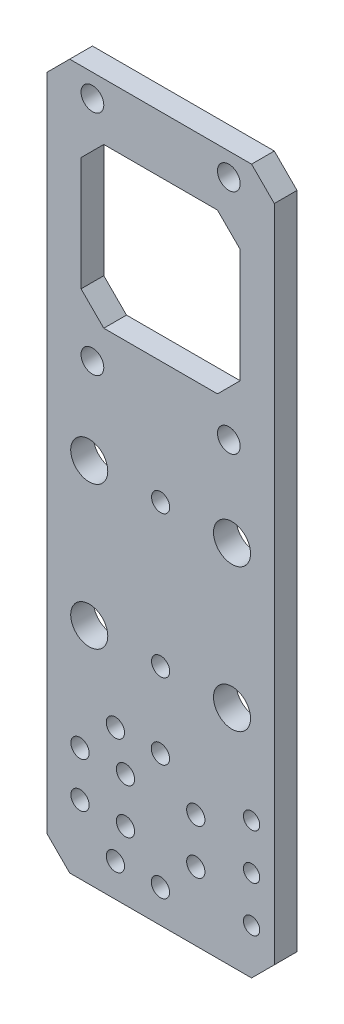
SolidWorks part; units mm, degrees
material "5052-O"
ref_plane "Front Plane" through (0, 0, 0) normal (0, 0, 1) x (1, 0, 0)
ref_plane "Top Plane" through (0, 0, 0) normal (0, 1, 0) x (1, 0, 0)
ref_plane "Right Plane" through (0, 0, 0) normal (1, 0, 0) x (0, 0, -1)
sketch "Sketch1" plane through (0, 0, 0) normal (0, 0, 1) x (1, 0, 0)
  line L1 (-31.75, -82.55) -> (31.75, -82.55)
  line L2 (-31.75, -82.55) -> (-31.75, 114.3)
  line L3 (-31.75, 114.3) -> (31.75, 114.3)
  line L4 (31.75, -82.55) -> (31.75, 114.3)
  line L5 (-31.75, -82.55) -> (31.75, 114.3) construction
  line L6 (-31.75, 114.3) -> (31.75, -82.55) construction
  point P0 (0, 0)
  point P7 (0, 114.3)
  dimension "D1" = 82.55
  dimension "D2" = 63.5
  dimension "D3" = 114.3
extrude "Boss-Extrude1" add sketch "Sketch1" along normal mid plane 6.35
sketch "Sketch2" plane through (0, 0, 3.175) normal (0, 0, 1) x (1, 0, 0)
  line L0 (31.75, 114.3) -> (-31.75, 114.3) construction
  line L1 (-19.939, 19.939) -> (19.939, 19.939) construction
  line L2 (-19.939, 19.939) -> (-19.939, -19.939) construction
  line L3 (-19.939, -19.939) -> (19.939, -19.939) construction
  line L4 (19.939, 19.939) -> (19.939, -19.939) construction
  line L5 (-19.939, 19.939) -> (19.939, -19.939) construction
  line L6 (-19.939, -19.939) -> (19.939, 19.939) construction
  line L9 (0, -19.85) -> (0, 19.85) construction
  circle A8 centre (-19.939, -19.939) radius 2 construction
  circle A9 centre (19.939, -19.939) radius 2 construction
  circle A10 centre (19.939, 19.939) radius 2 construction
  circle A11 centre (-19.939, 19.939) radius 2 construction
  arc A13 (2.5159, 20.1991) -> (2.5158, 20.2) centre (0, 19.85) ccw
  circle A14 centre (0, -19.85) radius 2.54
  circle A17 centre (0, 19.85) radius 2.54
  circle A18 centre (-19.939, 19.939) radius 5.175
  circle A19 centre (19.939, 19.939) radius 5.175
  circle A20 centre (19.939, -19.939) radius 5.175
  circle A21 centre (-19.939, -19.939) radius 5.175
  point P3 (0, 0)
  point P7 (0, 0)
  point P15 (0, 0)
  point P35 (0, 114.3)
  dimension "D5" = 10.35
  dimension "D4" = 5.08
  dimension "D2" = 39.878
  dimension "D3" = 39.7
  dimension "D1" = 3.175
extrude "Cut-Extrude1" cut sketch "Sketch2" against normal through all contours A11 | A10 | A13 A17 | A9 | A14 | A8 | A18 | A21 | A20 | A19 region at (0, 19.85, 3.175) region at (0, -19.85, 3.175) region at (-19.939, 19.939, 3.175) region at (19.939, 19.939, 3.175) region at (19.939, -19.939, 3.175) region at (-19.939, -19.939, 3.175)
sketch "Sketch3" plane through (0, 0, 3.175) normal (0, 0, 1) x (1, 0, 0)
  line L0 (31.75, 114.3) -> (-31.75, 114.3) construction
  line L1 (-22.225, 53.975) -> (22.225, 53.975)
  line L2 (-22.225, 53.975) -> (-22.225, 98.425)
  line L3 (-22.225, 98.425) -> (22.225, 98.425)
  line L4 (22.225, 53.975) -> (22.225, 98.425)
  line L5 (-22.225, 53.975) -> (22.225, 98.425) construction
  line L6 (-22.225, 98.425) -> (22.225, 53.975) construction
  point P0 (0, 76.2)
  point P9 (0, 114.3)
  dimension "D1" = 44.45
  dimension "D2" = 38.1
extrude "Cut-Extrude2" cut sketch "Sketch3" against normal through all
sketch "Sketch4" plane through (0, 0, 3.175) normal (0, 0, 1) x (1, 0, 0)
  line L0 (22.225, 98.425) -> (-22.225, 98.425) construction
  line L1 (-19.05, 44.45) -> (19.05, 44.45) construction
  line L2 (-19.05, 44.45) -> (-19.05, 107.95) construction
  line L3 (-19.05, 107.95) -> (19.05, 107.95) construction
  line L4 (19.05, 44.45) -> (19.05, 107.95) construction
  line L5 (-19.05, 44.45) -> (19.05, 107.95) construction
  line L6 (-19.05, 107.95) -> (19.05, 44.45) construction
  line L7 (-22.225, 98.425) -> (-22.225, 53.975) construction
  circle A0 centre (-19.05, 107.95) radius 3.175
  circle A1 centre (19.05, 107.95) radius 3.175
  circle A2 centre (19.05, 44.45) radius 3.175
  circle A3 centre (-19.05, 44.45) radius 3.175
  point P8 (0, 76.2)
  point P15 (0, 98.425)
  point P18 (-22.225, 76.2)
  dimension "D3" = 6.35
  dimension "D1" = 38.1
  dimension "D2" = 63.5
extrude "Cut-Extrude3" cut sketch "Sketch4" against normal through all
chamfer "Chamfer1" distance 6.35 angle 45 8 edges at (31.75, -82.55, 0) (-31.75, -82.55, 0) (31.75, 114.3, 0) (-31.75, 114.3, 0) (-22.225, 53.975, 0) (22.225, 53.975, 0) (22.225, 98.425, 0) (-22.225, 98.425, 0)
sketch "Sketch5" plane through (0, 0, -3.175) normal (0, 0, -1) x (-1, 0, 0)
  line L0 (-25.4, -44.45) -> (-25.4, -57.15) construction
  line L1 (-25.4, -57.15) -> (-25.4, -69.85) construction
  line L2 (25.4, -82.55) -> (-25.4, -82.55) construction
  line L3 (-31.75, -76.2) -> (-31.75, 107.95) construction
  circle A0 centre (-25.4, -44.45) radius 2.286
  circle A1 centre (-25.4, -57.15) radius 2.286
  circle A2 centre (-25.4, -69.85) radius 2.286
  dimension "D1" = 4.572
  dimension "D2" = 12.7
  dimension "D3" = 12.7
  dimension "D4" = 6.35
extrude "Cut-Extrude4" cut sketch "Sketch5" against normal through all
sketch "Sketch6" plane through (0, 0, 3.175) normal (0, 0, 1) x (1, 0, 0)
  line L0 (-22.5145, -50.8638) -> (-12.6362, -40.9855) construction
  line L1 (-22.5145, -50.8638) -> (-0.0638, -73.3145) construction
  line L2 (-12.6362, -40.9855) -> (9.8145, -63.4362) construction
  line L3 (-0.0638, -73.3145) -> (9.8145, -63.4362) construction
  line L4 (-12.6362, -40.9855) -> (-0.0638, -73.3145) construction
  line L5 (-25.4, -82.55) -> (25.4, -82.55) construction
  line L7 (-31.75, 107.95) -> (-31.75, -76.2) construction
  point P2 (-6.35, -57.15)
  point P3 (9.8145, -63.4362)
  point P5 (-12.6362, -40.9855)
  point P6 (-22.5145, -50.8638)
  point P7 (-0.0638, -73.3145)
  point P13 (4.8753, -68.3753)
  point P14 (-17.5753, -45.9247)
  point P15 (-11.2891, -62.0891)
  point P16 (-1.4109, -52.2109)
  dimension "D1" = 25.4
  dimension "D2" = 31.75
  dimension "D3" = 13.97
  dimension "D4" = 25.4
  dimension "D5" = 45
hole_wizard "#10 Clearance Hole1" positions "Sketch7" profile "Sketch8" hole size "#10" standard "ANSI Inch"
sketch "Sketch7" plane through (0, 0, 3.175) normal (0, 0, 1) x (1, 0, 0)
  point P0 (-22.5145, -50.8638)
  point P3 (-12.6362, -40.9855)
  point P6 (9.8145, -63.4362)
  point P9 (-0.0638, -73.3145)
sketch "Sketch8" plane through (-22.5145, -50.8638, 3.175) normal (1, 0, 0) x (0, -1, 0)
  line L0 (0, 0) -> (0, 20.5838)
  line L1 (0, 20.5838) -> (2.5527, 19.05)
  line L2 (2.5527, 19.05) -> (2.5527, 0)
  line L5 (2.5527, 0) -> (0, 0)
  line L10 (0, 20.5838) -> (-2.5527, 19.05) construction
  line L11 (0, -6.35) -> (0, 107.95) construction
  dimension "Hole Dia." = 5.1054
  dimension "Hole Depth" = 19.05
  dimension "Drill Angle" = 118
ref_plane "Plane1" through (-6.35, 0, 0) normal (-1, 0, 0) x (0, 0, 1)
mirror "Mirror1" about plane through (-6.35, 0, 0) normal (-1, 0, 0) of "#10 Clearance Hole1"
sketch "Sketch9" plane through (0, 0, 3.175) normal (0, 0, 1) x (1, 0, 0)
  circle A0 centre (-9.8145, -50.8638) radius 2.5527
  circle A1 centre (-9.8145, -63.4362) radius 2.5527
  circle A2 centre (-22.5145, -50.8638) radius 2.5527 construction
  point P4 (-22.5145, -63.4362)
  dimension "D1" = 12.7
extrude "Cut-Extrude6" cut sketch "Sketch9" against normal through all
